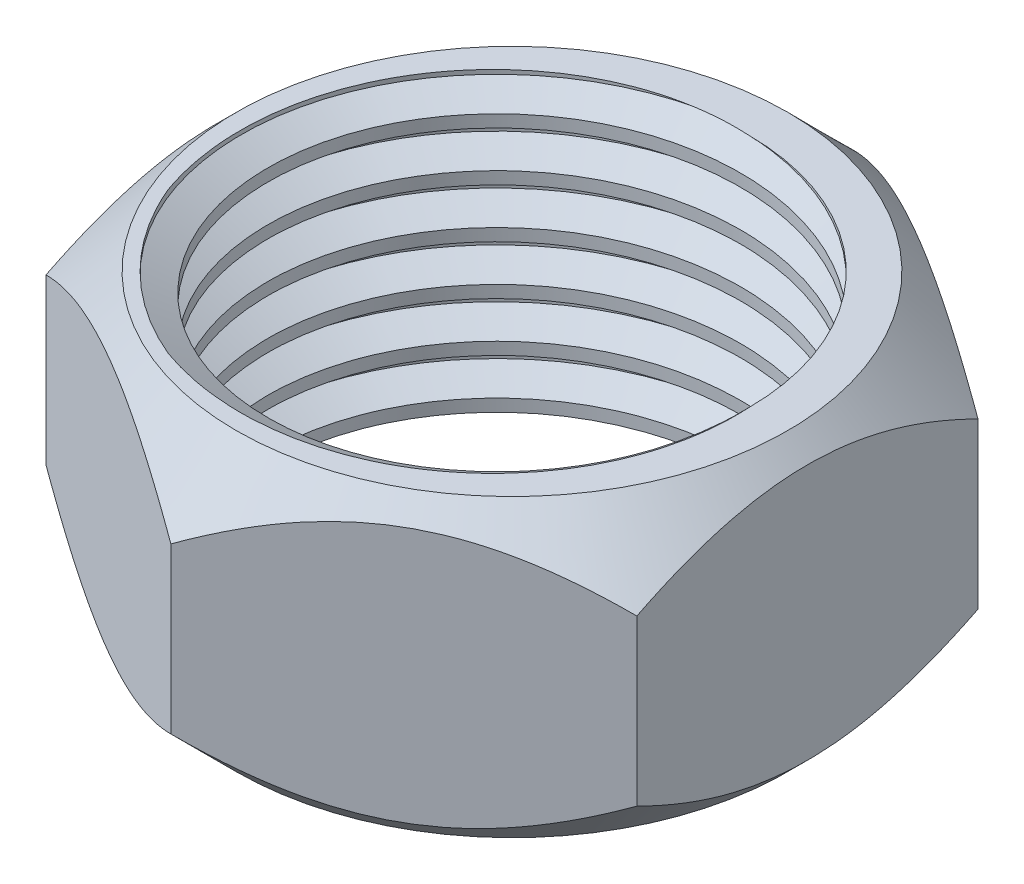
SolidWorks part; units mm, degrees
material "PBT General Purpose"
ref_plane "Front Plane" through (0, 0, 0) normal (0, 0, 1) x (1, 0, 0)
ref_plane "Top Plane" through (0, 0, 0) normal (0, 1, 0) x (1, 0, 0)
ref_plane "Right Plane" through (0, 0, 0) normal (1, 0, 0) x (0, 0, -1)
sketch "Sketch1" plane through (0, 0, 0) normal (0, 1, 0) x (1, 0, 0)
  line L1 (0, 8.6603) -> (-7.5, 4.3301)
  line L2 (-7.5, 4.3301) -> (-7.5, -4.3301)
  line L3 (-7.5, -4.3301) -> (0, -8.6603)
  line L4 (0, -8.6603) -> (7.5, -4.3301)
  line L5 (7.5, -4.3301) -> (7.5, 4.3301)
  line L6 (7.5, 4.3301) -> (0, 8.6603)
  circle A0 centre (0, 0) radius 7.5 construction
  dimension "D2" = 15
extrude "Boss-Extrude1" add sketch "Sketch1" along normal mid plane 7.5
sketch "Sketch9" plane through (0, 3.75, 0) normal (0, 1, 0) x (1, 0, 0)
  circle A0 centre (0, 0) radius 7
  dimension "D1" = 14
extrude "Cut-Extrude3" cut sketch "Sketch9" against normal through all draft 45 flip side to cut
mirror "Mirror1" about plane through (0, 0, 0) normal (0, 1, 0) of "Cut-Extrude3"
sketch "Sketch10" plane through (0, 3.75, 0) normal (0, 1, 0) x (1, 0, 0)
  circle A0 centre (0, 0) radius 6
  dimension "D1" = 12
extrude "Cut-Extrude4" cut sketch "Sketch10" against normal through all
thread "Thread1" pitch 1.25 start angle 0, offset 1.25, length 7.5, pitch 1.25, diameter 12
ref_plane "Plane2" through (6, -5, 0) normal (0, 0, 1) x (1, 0, 0)
sketch "Thread Profile2" plane through (6, -5, 0) normal (0, 0, 1) x (1, 0, 0)
  line L0 (0, 0) -> (0, 1.25) construction
  line L1 (0, 0) -> (0.6766, 0.3906)
  line L2 (0.6766, 0.3906) -> (0.6766, 0.5469)
  line L3 (0.6766, 0.5469) -> (0, 0.9375)
  line L4 (0.6766, 0.4687) -> (0, 0.4687) construction
  line L11 (0, 0) -> (0, 0.9375)
  point P2 (0, 0)
  dimension "Pitch" = 1.25
  dimension "Profile_Angle" = 60
  dimension "Profile_Land" = 0.1562
  dimension "Profile_Height" = 0.6766
